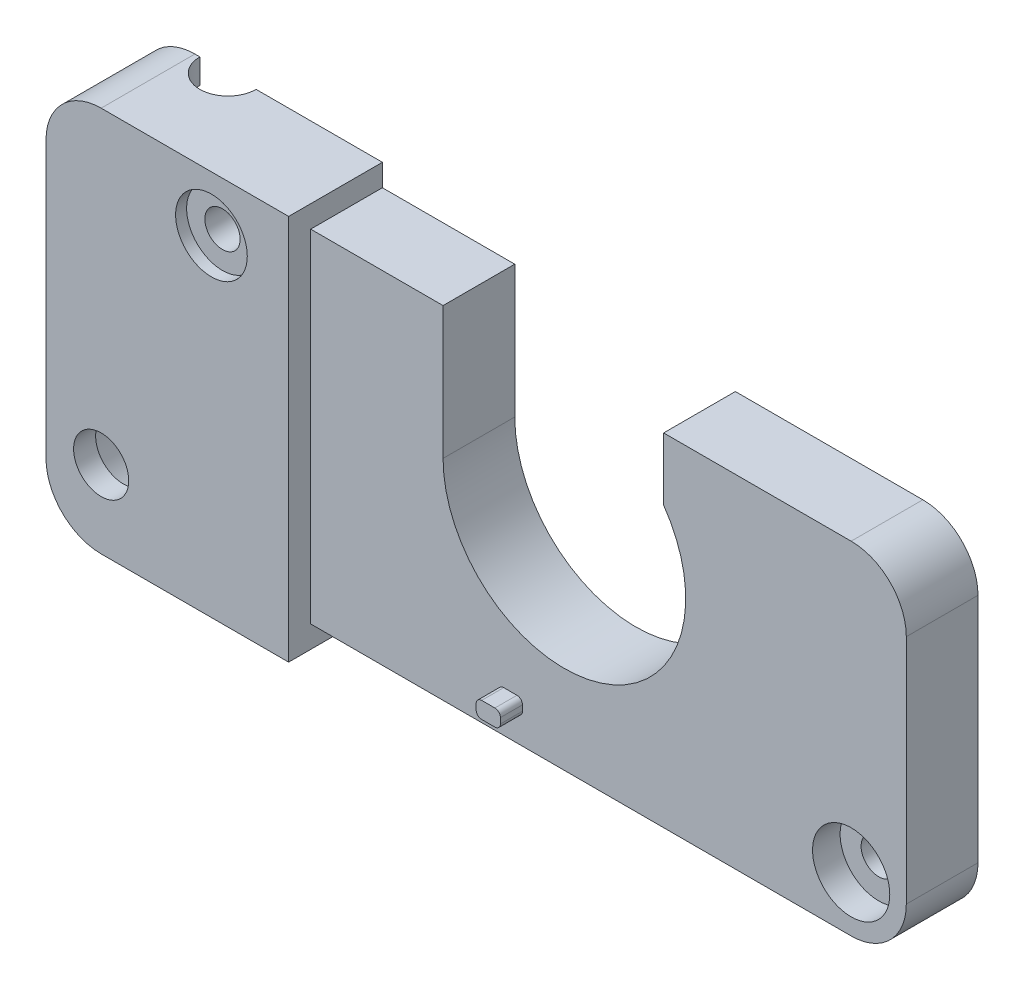
SolidWorks part; units mm, degrees
ref_plane "Front Plane" through (0, 0, 0) normal (0, 0, 1) x (1, 0, 0)
ref_plane "Top Plane" through (0, 0, 0) normal (0, 1, 0) x (1, 0, 0)
ref_plane "Right Plane" through (0, 0, 0) normal (1, 0, 0) x (0, 0, -1)
sketch "Sketch1" plane through (0, 0, 0) normal (0, 0, 1) x (1, 0, 0)
  line L0 (0, 21) -> (78, 21) construction
  line L1 (5, 0) -> (73, 0)
  line L2 (0, 5) -> (0, 30)
  line L3 (5, 35) -> (73, 35)
  line L4 (78, 5) -> (78, 30)
  line L5 (45, 35) -> (45, 0) construction
  line L6 (34, 21) -> (34, 35)
  line L7 (54, 35) -> (54, 27.3246)
  line L11 (22, 35) -> (22, 0) construction
  arc A0 (34, 21) -> (54, 27.3246) centre (45, 21) ccw
  arc A1 (5, 0) -> (0, 5) centre (5, 5) cw
  arc A2 (0, 30) -> (5, 35) centre (5, 30) cw
  arc A3 (73, 0) -> (78, 5) centre (73, 5) ccw
  arc A4 (78, 30) -> (73, 35) centre (73, 30) ccw
  point P18 (0, 0)
  point P21 (0, 35)
  point P24 (78, 0)
  dimension "D5" = 22
  dimension "D8" = 5
  dimension "D1" = 35
  dimension "D2" = 34
  dimension "D3" = 21
  dimension "D4" = 24
  dimension "D6" = 20
  dimension "D7" = 12
extrude "Boss-Extrude1" add sketch "Sketch1" along normal blind 17 contours L4 A4 L3 L7 A0 L6 A2 L2 A1 L1 A3 region at (2.069, 2.069, 0)
sketch "Sketch3" plane through (0, 0, 17) normal (0, 0, 1) x (1, 0, 0)
  line L0 (78, 5) -> (78, 30) construction
  line L1 (71, 33) -> (21, 33)
  line L2 (76, 28) -> (76, 7)
  line L3 (71, 2) -> (21, 2)
  line L4 (21, 33) -> (21, 2)
  line L6 (5, 0) -> (73, 0) construction
  line L7 (54, 35) -> (73, 35) construction
  line L8 (34, 21) -> (34, 35) construction
  line L9 (5, 35) -> (34, 35) construction
  line L10 (22, 35) -> (78, 35)
  line L11 (22, 35) -> (22, 0)
  line L12 (22, 0) -> (78, 0)
  line L13 (78, 35) -> (78, 0)
  arc A0 (71, 2) -> (76, 7) centre (71, 7) ccw
  arc A1 (76, 28) -> (71, 33) centre (71, 28) ccw
  line M9 (78, 5) -> (78, 30)
  arc M10 (78, 30) -> (73, 35) centre (73, 30) ccw
  line M11 (73, 35) -> (54, 35)
  line M12 (54, 35) -> (54, 27.3246)
  arc M13 (54, 27.3246) -> (34, 21) centre (45, 21) cw
  line M14 (34, 21) -> (34, 35)
  line M15 (34, 35) -> (5, 35)
  line M19 (5, 0) -> (73, 0)
  arc M20 (73, 0) -> (78, 5) centre (73, 5) ccw
  dimension "D5" = 5
  dimension "D1" = 2
  dimension "D2" = 2
  dimension "D3" = 2
  dimension "D4" = 13
  dimension "D6" = 2
  dimension "D7" = 2
  dimension "D8" = 12
extrude "Cut-Extrude1" cut sketch "Sketch3" against normal blind 17 contours L11 L1 M15 M14 | A1 L2 A0 L3 L11 L1 M19 M20 M9 M10 M11 M12 region at (62.5, 33.6604, 17) region at (28, 34, 17)
extrude "Cut-Extrude2" cut sketch "Sketch3<3>" against normal blind 2 contours L2 A1 L1 L4 L3 A0 M12 M13 M14 region at (74.0952, 31.0952, 17)
sketch "Sketch3<3>" plane through (0, 0, 17) normal (0, 0, 1) x (1, 0, 0) same geometry as "Sketch3"
sketch "Sketch5" plane through (0, 0, 0) normal (0, 0, -1) x (-1, 0, 0)
  line L1 (-22, 33) -> (-82, 33)
  line L2 (-22, 33) -> (-22, -2)
  line L3 (-22, -2) -> (-82, -2)
  line L4 (-82, 33) -> (-82, -2)
  dimension "D1" = 60
  dimension "D2" = 35
extrude "Cut-Extrude3" cut sketch "Sketch5" against normal blind 2
ref_plane "Plane1" through (0, 0, 14) normal (0, 0, 1) x (1, 0, 0)
sketch "Sketch6" plane through (0, 0, 14) normal (0, 0, 1) x (1, 0, 0)
  line L0 (22, 35) -> (22, 0) construction
  line L1 (22, 32) -> (69.5, 32)
  line L2 (22, 32) -> (22, 3)
  line L3 (22, 3) -> (69.5, 3)
  line L4 (74.5, 27) -> (74.5, 8)
  line L5 (76, 28) -> (76, 7) construction
  line L6 (71, 2) -> (22, 2) construction
  line L7 (71, 33) -> (54, 33) construction
  arc A0 (69.5, 3) -> (74.5, 8) centre (69.5, 8) ccw
  arc A1 (74.5, 27) -> (69.5, 32) centre (69.5, 27) ccw
  dimension "D4" = 5
  dimension "D1" = 1.5
  dimension "D2" = 1
  dimension "D3" = 1
extrude "Cut-Extrude4" cut sketch "Sketch6" against normal blind 11
sketch "Sketch11" plane through (0, 0, 15) normal (0, 0, 1) x (1, 0, 0)
  line L0 (0, 5) -> (0, 30) construction
  line L1 (22, 2) -> (7, 2)
  line L2 (22, 2) -> (22, 33)
  line L3 (22, 33) -> (7, 33)
  line L4 (2, 7) -> (2, 28)
  arc A0 (7, 2) -> (2, 7) centre (7, 7) cw
  arc A1 (7, 33) -> (2, 28) centre (7, 28) ccw
  dimension "D3" = 5
  dimension "D1" = 2
  dimension "D2" = 31
extrude "Cut-Extrude11" cut sketch "Sketch11" against normal blind 13
sketch "Sketch12" plane through (0, 0, 15) normal (0, 0, 1) x (1, 0, 0)
  line L0 (22, 33) -> (22, 2) construction
  line L1 (39.5, 5.75) -> (40.7, 5.75)
  line L2 (39, 5.25) -> (39, 4.75)
  line L3 (39.5, 4.25) -> (40.7, 4.25)
  line L4 (41.2, 5.25) -> (41.2, 4.75)
  line L7 (5, 0) -> (22, 0) construction
  arc A0 (41.2, 4.75) -> (40.7, 4.25) centre (40.7, 4.75) cw
  arc A1 (41.2, 5.25) -> (40.7, 5.75) centre (40.7, 5.25) ccw
  arc A2 (39, 4.75) -> (39.5, 4.25) centre (39.5, 4.75) ccw
  arc A3 (39, 5.25) -> (39.5, 5.75) centre (39.5, 5.25) cw
  point P10 (41.2, 4.25)
  point P15 (39, 4.25)
  point P18 (39, 5.75)
  dimension "D5" = 0.5
  dimension "D1" = 2.2
  dimension "D2" = 1.5
  dimension "D3" = 17
  dimension "D4" = 5.75
extrude "Boss-Extrude2" add sketch "Sketch12" along normal blind 2
sketch "Sketch13" plane through (0, 0, 17) normal (0, 0, 1) x (1, 0, 0)
  line L0 (5, 35) -> (5, 0) construction
  line L1 (5, 35) -> (22, 35) construction
  line L2 (5, 0) -> (22, 0) construction
  line L3 (0, 5) -> (0, 30) construction
  line L4 (0, 7) -> (22, 7) construction
  line L5 (22, 33) -> (22, 2) construction
  circle A0 centre (5, 7) radius 2.5
  dimension "D1" = 5
  dimension "D2" = 5
  dimension "D3" = 28
extrude "Cut-Extrude12" cut sketch "Sketch13" against normal blind 5
sketch "Sketch14" plane through (0, 35, 0) normal (0, 1, 0) x (1, 0, 0)
  line L0 (5, -8.5) -> (22, -8.5) construction
  line L1 (5, -17) -> (5, 0) construction
  line L2 (22, -2) -> (22, -15) construction
  line L3 (8, 0) -> (8, -17) construction
  line L6 (5, 0) -> (22, 0) construction
  line L7 (5, -17) -> (22, -17) construction
  line L8 (0, -17) -> (0, 0) construction
  circle A1 centre (8, -8.5) radius 2.55
  dimension "D2" = 5.1
  dimension "D1" = 8
extrude "Cut-Extrude14" cut sketch "Sketch14" against normal blind 15
sketch "Sketch15" plane through (0, 0, 17) normal (0, 0, 1) x (1, 0, 0)
  line L0 (15, 35) -> (15, 0) construction
  line L1 (5, 35) -> (22, 35) construction
  line L2 (5, 0) -> (22, 0) construction
  line L3 (0, 30) -> (22, 30) construction
  line L4 (0, 5) -> (0, 30) construction
  line L5 (22, 33) -> (22, 2) construction
  circle A0 centre (15, 30) radius 3.25
  circle A1 centre (15, 30) radius 1.6
  dimension "D3" = 6.5
  dimension "D4" = 3.2
  dimension "D1" = 15
  dimension "D2" = 5
extrude "Boss-Extrude5" add sketch "Sketch15" against normal through all
extrude "Cut-Extrude16" cut sketch "Sketch15<4>" against normal blind 1
sketch "Sketch15<4>" plane through (0, 0, 17) normal (0, 0, 1) x (1, 0, 0) same geometry as "Sketch15"
sketch "Sketch18" plane through (0, 0, 17) normal (0, 0, 1) x (1, 0, 0)
  circle A0 centre (15, 30) radius 1.6
  dimension "D1" = 3.2
extrude "Cut-Extrude17" cut sketch "Sketch18" against normal blind 15
sketch "Sketch20" plane through (0, 0, 15) normal (0, 0, 1) x (1, 0, 0)
  line L0 (71, 33) -> (71, 2) construction
  line L1 (71, 33) -> (54, 33) construction
  line L2 (71, 2) -> (22, 2) construction
  line L3 (76, 7) -> (22, 7) construction
  line L4 (22, 33) -> (22, 2) construction
  line L5 (76, 28) -> (76, 7) construction
  arc A0 (71, 2) -> (76, 7) centre (71, 7) ccw construction
  circle A1 centre (71, 7) radius 4.5
  circle A2 centre (71, 7) radius 1.6
  dimension "D3" = 9
  dimension "D4" = 3.2
  dimension "D1" = 5
  dimension "D2" = 5
extrude "Boss-Extrude6" add sketch "Sketch20" against normal blind 13
extrude "Cut-Extrude20" cut sketch "Sketch20<3>" against normal through all from surface contours A2 starting at face at (52.0388, 20.5674, 15)
sketch "Sketch20<3>" plane through (0, 0, 15) normal (0, 0, 1) x (1, 0, 0) same geometry as "Sketch20"
sketch "Sketch21" plane through (0, 0, 2) normal (0, 0, -1) x (-1, 0, 0)
  circle A0 centre (-71, 7) radius 3.5
  dimension "D1" = 7
ref_plane "Plane13" through (0, 0, 8.5) normal (0, 0, 1) x (1, 0, 0)
sketch "Sketch22" plane through (22, 0, 0) normal (1, 0, 0) x (0, 0, -1)
  line L0 (-2, 2) -> (-15, 2) construction
  line L1 (-15, 33) -> (-2, 33)
  line L2 (-15, 33) -> (-15, 2)
  line L3 (-15, 2) -> (-2, 2)
  line L4 (-2, 33) -> (-2, 2)
  line L5 (-2, 2) -> (-15, 2) construction
  line L6 (-14, 17.05) -> (-14, -17.05) construction
  line L11 (-14, 32) -> (-3, 32)
  line L12 (-14, 32) -> (-14, 3)
  line L13 (-14, 3) -> (-3, 3)
  line L14 (-3, 32) -> (-3, 3)
  line L15 (0, 35) -> (0, 0) construction
  dimension "D1" = 2
  dimension "D2" = 1
  dimension "D3" = 1
  dimension "D4" = 1
extrude "Boss-Extrude7" add sketch "Sketch22" against normal blind 3
sketch "Sketch24" plane through (0, 0, 8.5) normal (0, 0, 1) x (1, 0, 0)
  line L1 (0, 0) -> (80, 0)
  line L2 (0, 0) -> (0, 36)
  line L3 (0, 36) -> (80, 36)
  line L4 (80, 0) -> (80, 36)
  dimension "D1" = 36
  dimension "D2" = 80
extrude "Cut-Extrude21" cut sketch "Sketch21" against normal blind 2
sketch "Sketch29" plane through (0, 0, 15) normal (0, 0, 1) x (1, 0, 0)
  circle A0 centre (71, 7) radius 3.5
  dimension "D1" = 7
extrude "Cut-Extrude22" cut sketch "Sketch29" against normal blind 2.5
sketch "Sketch36" plane through (0, 0, 15) normal (0, 0, 1) x (1, 0, 0)
  line L0 (34, 33) -> (34, 21)
  line L1 (54, 27.3246) -> (54, 33)
  line L2 (54, 33) -> (54.7, 33)
  line L3 (71, 33) -> (54, 33) construction
  line L4 (54.7, 33) -> (54.7, 27.3246)
  line L5 (33.3, 21) -> (33.3, 33)
  line L6 (34, 33) -> (22, 33) construction
  line L7 (33.3, 33) -> (34, 33)
  line L15 (76, 7) -> (76, 28)
  line L16 (71, 33) -> (54, 33)
  line L17 (54, 33) -> (54, 27.3246)
  line L18 (34, 21) -> (34, 33)
  line L19 (34, 33) -> (22, 33)
  line L20 (22, 33) -> (22, 2)
  line L21 (22, 2) -> (71, 2)
  line L23 (54.7, 33) -> (54, 33)
  line L24 (54, 33) -> (54, 27.3246)
  line L25 (34, 21) -> (34, 33)
  line L26 (34, 33) -> (33.3, 33)
  arc A2 (33.3, 21) -> (54.7, 27.3246) centre (44.998, 20.7853) ccw
  arc A4 (34, 21) -> (54, 27.3246) centre (45, 21) ccw
  arc A7 (76, 28) -> (71, 33) centre (71, 28) ccw
  arc A8 (34, 21) -> (54, 27.3246) centre (45, 21) ccw
  arc A9 (71, 2) -> (76, 7) centre (71, 7) ccw
  line M9 (71, 33) -> (54, 33)
  line M10 (54, 33) -> (54, 27.3246)
  arc M11 (54, 27.3246) -> (34, 21) centre (45, 21) cw
  line M12 (34, 21) -> (34, 33)
  line M13 (34, 33) -> (22, 33)
  dimension "D3" = 11.7
  dimension "D1" = 0.7
  dimension "D2" = 0.7
  dimension "D4" = 0
extrude "Boss-Extrude10" add sketch "Sketch36" against normal up to surface (13 mm away) contours L5 A2 L4 M9 M10 M11 M12 M13 region at (33.6654, 27, 15) up to face at (67.5, 7, 2)
extrude "Cut-Extrude23" cut sketch "Sketch24" against normal blind 10
